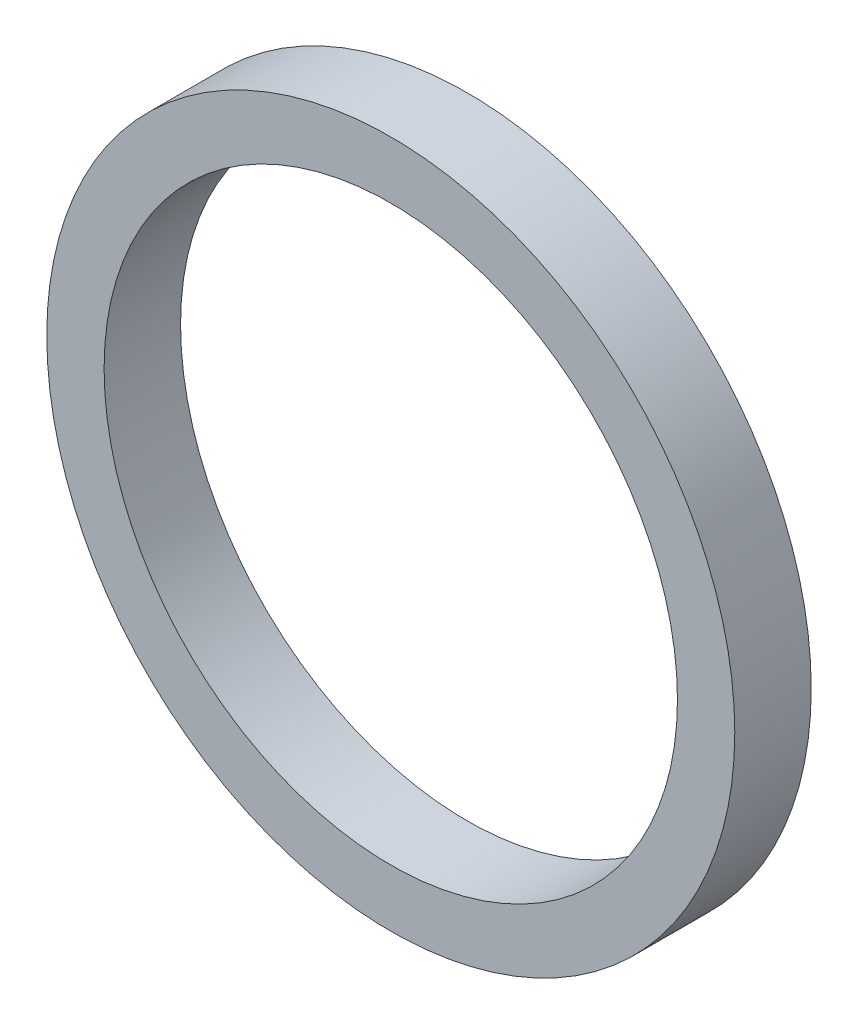
SolidWorks part; units mm, degrees
ref_plane "Front" through (0, 0, 0) normal (0, 0, 1) x (1, 0, 0)
ref_plane "Top" through (0, 0, 0) normal (0, 1, 0) x (1, 0, 0)
ref_plane "Right" through (0, 0, 0) normal (1, 0, 0) x (0, 0, -1)
sketch "Sketch1" plane through (0, 0, 0) normal (0, 0, 1) x (1, 0, 0)
  circle A0 centre (0, 0) radius 18
  circle A1 centre (0, 0) radius 15
  dimension "d" = 30
  dimension "D0" = 36
extrude "Base-Extrude" add sketch "Sketch1" against normal blind 4
